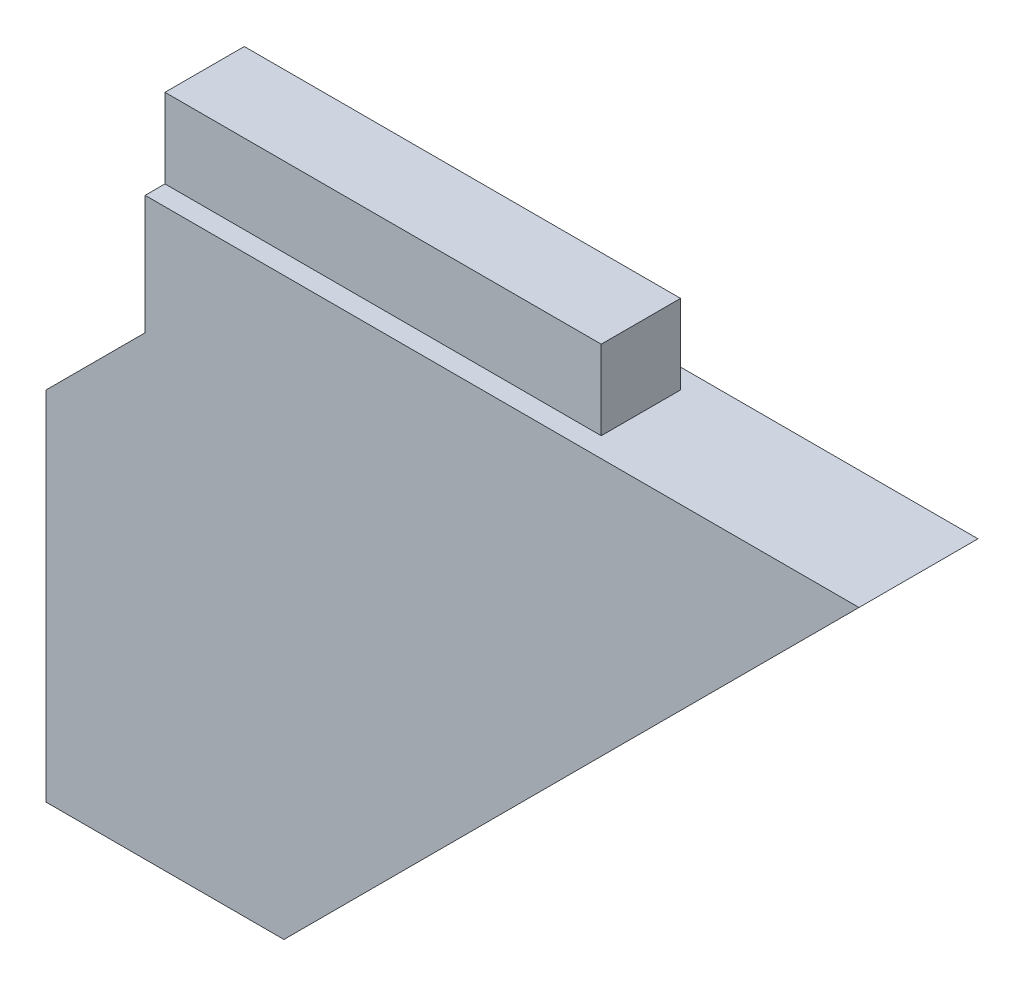
SolidWorks part; units mm, degrees
ref_plane "Front Plane" through (0, 0, 0) normal (0, 0, 1) x (1, 0, 0)
ref_plane "Top Plane" through (0, 0, 0) normal (0, 1, 0) x (1, 0, 0)
ref_plane "Right Plane" through (0, 0, 0) normal (1, 0, 0) x (0, 0, -1)
sketch "Sketch1" plane through (0, 0, 0) normal (0, 0, 1) x (1, 0, 0)
  line L1 (-39.5, -6) -> (-28.5, -6)
  line L13 (-28.5, -4) -> (-28.5, -6)
  line L14 (-39.5, -4) -> (-28.5, -4)
  line L15 (-39.5, -4) -> (-39.5, -6)
  line L16 (-28.5, -4) -> (-28.5, -6)
  line L17 (-36, -20.5) -> (-24.0089, -8.5089)
  line L21 (-42, -20.5) -> (-36, -20.5)
  line L22 (-42, -11.5) -> (-42, -20.5)
  line L23 (-39.5, -9) -> (-42, -11.5)
  line L24 (-39.5, -6) -> (-39.5, -9)
  line L25 (-24.0089, -8.5089) -> (-21.5, -6)
  line L26 (-28.5, -6) -> (-21.5, -6)
  dimension "D1" = 3
  dimension "D2" = 2.5
  dimension "D3" = 9
  dimension "D4" = 6
  dimension "D5" = 7
  dimension "D6" = 11
  dimension "D8" = 2.5
  dimension "D9" = 2
extrude "Boss-Extrude1" add sketch "Sketch1" along normal mid plane 3 contours L1 L24 L23 L22 L21 region at (-34.3533, -12.1467, 0)
extrude "Boss-Extrude2" add sketch "Sketch1<4>" along normal mid plane 2 contours L14 L15 L1 L13 region at (-34, -5, 0)
sketch "Sketch1<4>" plane through (0, 0, 0) normal (0, 0, 1) x (1, 0, 0) same geometry as "Sketch1"
